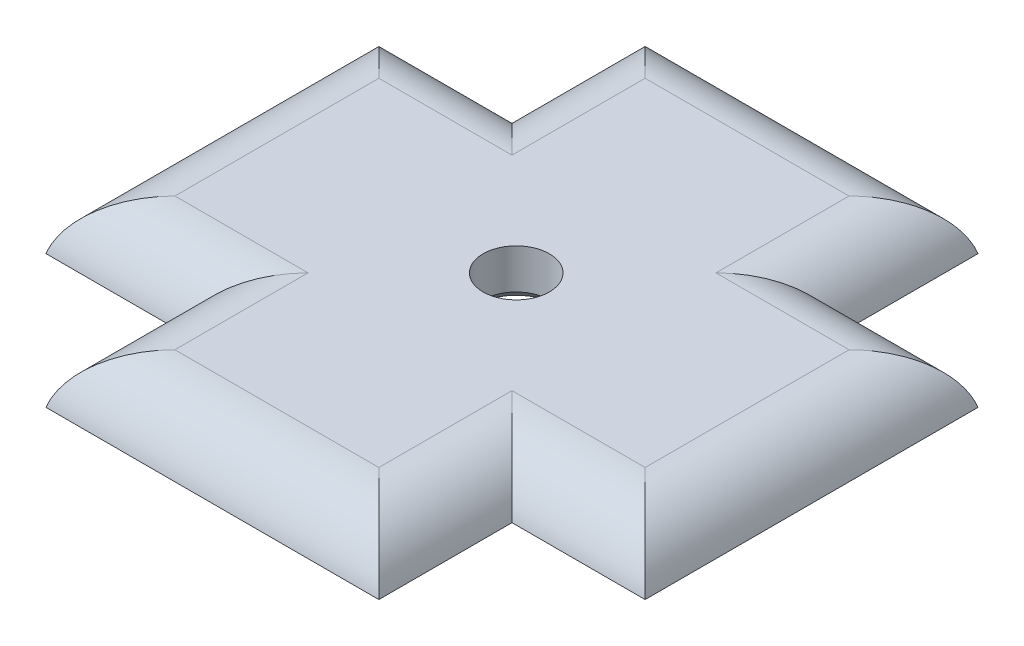
SolidWorks part; units mm, degrees
ref_plane "Front Plane" through (0, 0, 0) normal (0, 0, 1) x (1, 0, 0)
ref_plane "Top Plane" through (0, 0, 0) normal (0, 1, 0) x (1, 0, 0)
ref_plane "Right Plane" through (0, 0, 0) normal (1, 0, 0) x (0, 0, -1)
sketch "Sketch1" plane through (0, 0, 0) normal (0, 1, 0) x (1, 0, 0)
  line L1 (0, 0) -> (90, 0)
  line L2 (0, 0) -> (0, -90)
  line L3 (0, -90) -> (90, -90)
  line L4 (90, 0) -> (90, -90)
  line L5 (0, 0) -> (20, 0)
  line L6 (0, 0) -> (0, -20)
  line L7 (0, -20) -> (20, -20)
  line L8 (20, 0) -> (20, -20)
  line L9 (90, 0) -> (70, 0)
  line L10 (90, 0) -> (90, -20)
  line L11 (90, -20) -> (70, -20)
  line L12 (70, 0) -> (70, -20)
  line L13 (0, -90) -> (20, -90)
  line L14 (0, -90) -> (0, -70)
  line L15 (0, -70) -> (20, -70)
  line L16 (20, -90) -> (20, -70)
  line L17 (90, -90) -> (70, -90)
  line L18 (90, -90) -> (90, -70)
  line L19 (90, -70) -> (70, -70)
  line L20 (70, -90) -> (70, -70)
  dimension "D1" = 90
  dimension "D2" = 90
  dimension "D3" = 20
  dimension "D4" = 20
  dimension "D5" = 20
  dimension "D6" = 20
  dimension "D7" = 20
  dimension "D8" = 20
  dimension "D9" = 20
  dimension "D10" = 20
extrude "Boss-Extrude1" add sketch "Sketch1" along normal blind 7.5 contours L3 L20 L19 L4 L11 L12 L1 L8 L7 L2 L15 L16 region at (45, 0, 45)
fillet "Fillet1" radius 10 12 edges at (10, 7.5, 70) (20, 7.5, 80) (70, 7.5, 80) (80, 7.5, 70) (80, 7.5, 20) (70, 7.5, 10) (20, 7.5, 10) (10, 7.5, 20) (45, 7.5, 90) (90, 7.5, 45) (45, 7.5, 0) (0, 7.5, 45)
sketch "Sketch2" plane through (0, 7.5, 0) normal (0, 1, 0) x (1, 0, 0)
  line L0 (80.3175, -60.3175) -> (80.3175, -29.6825) construction
  line L1 (60.3175, -9.6825) -> (29.6825, -9.6825) construction
  circle A0 centre (45.3175, -44.6825) radius 4.975
  dimension "D1" = 9.95
  dimension "D2" = 35
  dimension "D3" = 35
extrude "Cut-Extrude1" cut sketch "Sketch2" against normal blind 7.5
chamfer "Chamfer1" distance 1.5 angle 45 1 edges at (45.3175, 0, 49.6575)
